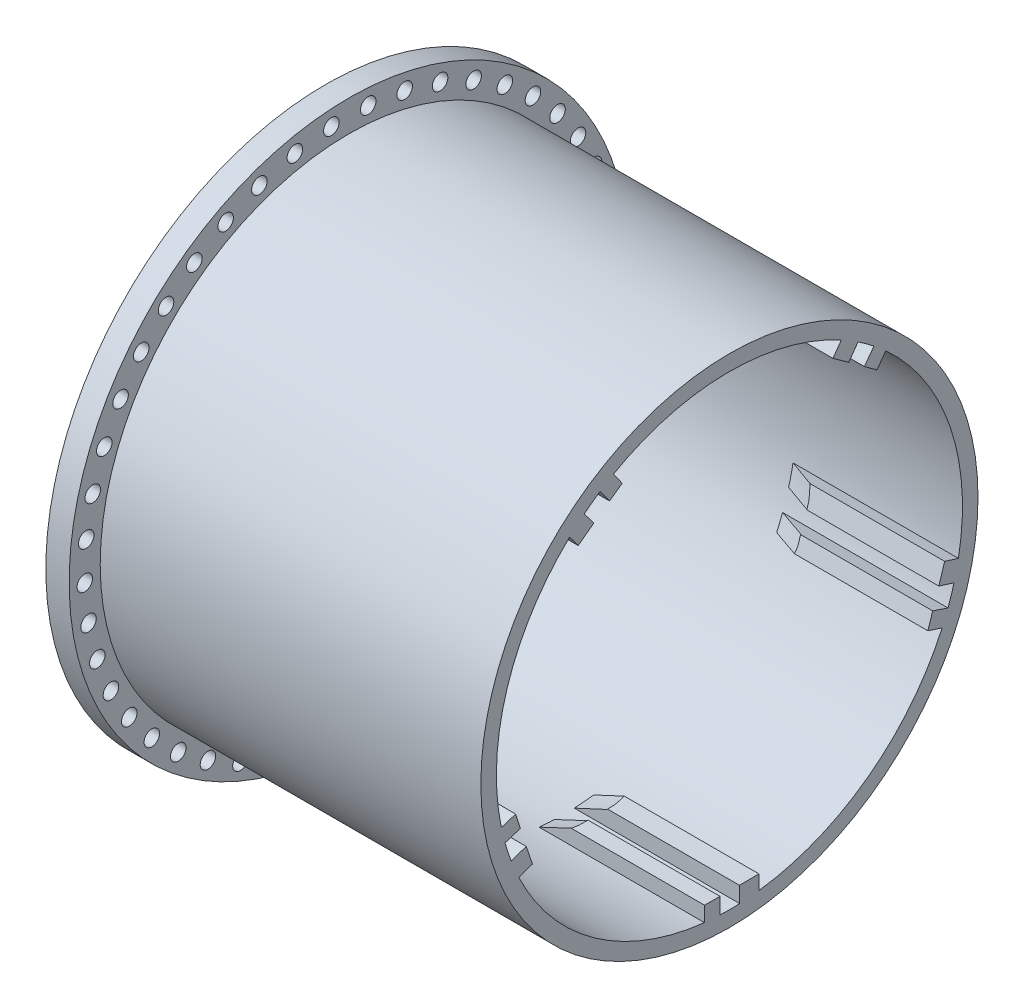
SolidWorks part; units mm, degrees
material "ABS"
ref_plane "Front Plane" through (0, 0, 0) normal (0, 0, 1) x (1, 0, 0)
ref_plane "Top Plane" through (0, 0, 0) normal (0, 1, 0) x (1, 0, 0)
ref_plane "Right Plane" through (0, 0, 0) normal (1, 0, 0) x (0, 0, -1)
sketch "Sketch1" plane through (0, 0, 0) normal (1, 0, 0) x (0, 0, -1)
  line L0 (0, 0) -> (20.089, 27.4305) construction
  line L1 (-2, 1.5) -> (2, 1.5)
  line L3 (-2, -1.5) -> (2, -1.5)
  line L5 (-2, 1.5) -> (2, -1.5) construction
  line L6 (-2, -1.5) -> (2, 1.5) construction
  circle A0 centre (0, 0) radius 30
  arc A1 (-2, 1.5) -> (-2, -1.5) centre (0, 0) ccw
  arc A2 (2, -1.5) -> (2, 1.5) centre (0, 0) ccw
  circle A3 centre (20.089, 27.4305) radius 1
  circle A4 centre (23.7111, 24.3677) radius 1
  circle A5 centre (26.8717, 20.8306) radius 1
  circle A6 centre (29.5092, 16.888) radius 1
  circle A7 centre (31.5724, 12.6168) radius 1
  circle A8 centre (33.0211, 8.1) radius 1
  circle A9 centre (33.827, 3.4255) radius 1
  circle A10 centre (33.9745, -1.3156) radius 1
  circle A11 centre (33.4608, -6.0312) radius 1
  circle A12 centre (32.2958, -10.6293) radius 1
  circle A13 centre (30.5022, -15.0206) radius 1
  circle A14 centre (28.1149, -19.1195) radius 1
  circle A15 centre (25.1803, -22.8463) radius 1
  circle A16 centre (21.7557, -26.1283) radius 1
  circle A17 centre (17.9076, -28.9019) radius 1
  circle A18 centre (13.711, -31.1129) radius 1
  circle A19 centre (9.2475, -32.7183) radius 1
  circle A20 centre (4.604, -33.6868) radius 1
  circle A21 centre (-0.1292, -33.9998) radius 1
  circle A22 centre (-4.8597, -33.6509) radius 1
  circle A23 centre (-9.4957, -32.6471) radius 1
  circle A24 centre (-13.9469, -31.0078) radius 1
  circle A25 centre (-18.1267, -28.765) radius 1
  circle A26 centre (-21.9536, -25.9623) radius 1
  circle A27 centre (-25.3532, -22.6543) radius 1
  circle A28 centre (-28.2593, -18.9054) radius 1
  circle A29 centre (-30.6154, -14.7884) radius 1
  circle A30 centre (-32.3756, -10.3837) radius 1
  circle A31 centre (-33.5056, -5.7768) radius 1
  circle A32 centre (-33.9836, -1.0575) radius 1
  circle A33 centre (-33.8, 3.6824) radius 1
  circle A34 centre (-32.9586, 8.3506) radius 1
  circle A35 centre (-31.4756, 12.8563) radius 1
  circle A36 centre (-29.3801, 17.1117) radius 1
  circle A37 centre (-26.7127, 21.0341) radius 1
  circle A38 centre (-23.5253, 24.5471) radius 1
  circle A39 centre (-19.8801, 27.5823) radius 1
  circle A40 centre (-15.8479, 30.0806) radius 1
  circle A41 centre (-11.5072, 31.9935) radius 1
  circle A42 centre (-6.9426, 33.2836) radius 1
  circle A43 centre (-2.2429, 33.9259) radius 1
  circle A44 centre (2.5005, 33.9079) radius 1
  circle A45 centre (7.1953, 33.2299) radius 1
  circle A46 centre (11.75, 31.9051) radius 1
  circle A47 centre (16.076, 29.9594) radius 1
  circle A48 centre (0, 0) radius 4.25
  circle A49 centre (0, 0) radius 36
  circle A50 centre (0, 0) radius 32
  dimension "D1" = 60
  dimension "D4" = 2
  dimension "D7" = 8.5
  dimension "D8" = 72
  dimension "D2" = 4
  dimension "D3" = 3
  dimension "D5" = 34
  dimension "D9" = 2
  dimension "D6" = 45
extrude "Boss-Extrude1" add sketch "Sketch1" along normal blind 3 contours A0 A48 | A50 A0 | A49 A50 A3 A4 A5 A6 A7 A8 A9 A10 A11 A12 A13 A14 A15 A16 A17 A18 A19 A20 A21 A22 A23 A24 A25 A26 region at (0, 0, 29.1515) region at (0, 0, 34.9818) region at (0, 0, 31.0949)
sketch "Sketch2" plane through (3, 0, 0) normal (1, 0, 0) x (0, 0, -1)
  line L0 (-26.1553, -9.8616) -> (-28.0974, -10.5135)
  line L1 (-1.2034, -27.9057) -> (-1.2173, -29.9753)
  line L2 (1.2965, -27.9225) -> (1.3164, -29.9711)
  line L3 (-26.9118, -7.4788) -> (-28.8844, -8.1051)
  line L4 (-17.4614, 21.8277) -> (-18.6815, 23.4734)
  line L5 (-15.429, 23.2835) -> (-16.6342, 24.9661)
  line L6 (15.3635, 23.3519) -> (16.5516, 25.0209)
  line L7 (17.3761, 21.8688) -> (18.6039, 23.535)
  line L8 (26.9566, -7.3954) -> (28.911, -8.0096)
  line L9 (26.168, -9.7678) -> (28.132, -10.4206)
  line L11 (-27.517, -5.5726) -> (-29.3612, -6.1581)
  line L13 (-26.1553, -9.8616) -> (-28.1279, -10.4879)
  line L14 (-25.3597, -12.2317) -> (-27.1214, -12.823)
  line L15 (-26.9118, -7.4788) -> (-27.517, -5.5726)
  line L16 (-26.1553, -9.8616) -> (-25.3597, -12.2317)
  line L17 (-25.3597, -12.2317) -> (-27.3019, -12.8836) construction
  line L18 (-27.517, -5.5726) -> (-29.4896, -6.1989) construction
  line L19 (-13.8031, 24.4482) -> (-14.9298, 26.0212)
  line L20 (-15.429, 23.2835) -> (-13.8031, 24.4482)
  line L21 (-15.429, 23.2835) -> (-16.6342, 24.9661)
  line L22 (-17.4614, 21.8277) -> (-18.6815, 23.4734)
  line L23 (-17.4614, 21.8277) -> (-19.4696, 20.3387)
  line L24 (-19.4696, 20.3387) -> (-20.5764, 21.8315)
  line L25 (18.9862, 20.6824) -> (20.134, 22.2401)
  line L26 (17.3761, 21.8688) -> (18.9862, 20.6824)
  line L27 (17.3761, 21.8688) -> (18.6039, 23.535)
  line L28 (15.3635, 23.3519) -> (16.5516, 25.0209)
  line L29 (15.3635, 23.3519) -> (13.3269, 24.8017)
  line L30 (13.3269, 24.8017) -> (14.4045, 26.3156)
  line L31 (25.5372, -11.6657) -> (27.3733, -12.276)
  line L32 (26.168, -9.7678) -> (25.5372, -11.6657)
  line L33 (26.168, -9.7678) -> (28.132, -10.4206)
  line L34 (26.9566, -7.3954) -> (28.911, -8.0096)
  line L35 (26.9566, -7.3954) -> (27.7061, -5.0104)
  line L36 (27.7061, -5.0104) -> (29.4788, -5.5676)
  line L37 (-3.2034, -27.8922) -> (-3.2164, -29.8271)
  line L38 (-1.2034, -27.9057) -> (-3.2034, -27.8922)
  line L39 (-1.2034, -27.9057) -> (-1.2173, -29.9753)
  line L40 (1.2965, -27.9225) -> (1.3164, -29.9711)
  line L41 (1.2965, -27.9225) -> (3.7964, -27.8983)
  line L42 (3.7964, -27.8983) -> (3.8144, -29.7565)
  circle A2 centre (0, 0) radius 30 construction
  arc A3 (-1.2173, -29.9753) -> (1.3164, -29.9711) centre (0, 0) ccw
  arc A5 (-28.8844, -8.1051) -> (-28.0974, -10.5135) centre (0, 0) ccw
  arc A7 (-16.6342, 24.9661) -> (-18.6815, 23.4734) centre (0, 0) ccw
  arc A9 (18.6039, 23.535) -> (16.5516, 25.0209) centre (0, 0) ccw
  arc A11 (28.132, -10.4206) -> (28.911, -8.0096) centre (0, 0) ccw
  arc A12 (-28.8844, -8.1051) -> (-28.0974, -10.5135) centre (0, 0) ccw
  circle A13 centre (0, 0) radius 32 construction
  circle A14 centre (0, 0) radius 32
  arc A15 (-27.1214, -12.823) -> (-3.2164, -29.8271) centre (0, 0) ccw
  arc A20 (28.132, -10.4206) -> (28.911, -8.0096) centre (0, 0) ccw
  arc A21 (29.4788, -5.5676) -> (20.134, 22.2401) centre (0, 0) ccw
  arc A22 (14.4045, 26.3156) -> (-14.9298, 26.0212) centre (0, 0) ccw
  arc A23 (18.6039, 23.535) -> (16.5516, 25.0209) centre (0, 0) ccw
  arc A24 (-20.5764, 21.8315) -> (-29.3612, -6.1581) centre (0, 0) ccw
  arc A25 (-16.6342, 24.9661) -> (-18.6815, 23.4734) centre (0, 0) ccw
  arc A26 (-1.2173, -29.9753) -> (1.3164, -29.9711) centre (0, 0) ccw
  arc A27 (3.8144, -29.7565) -> (27.3733, -12.276) centre (0, 0) ccw
  dimension "D2" = 2
  dimension "D1" = 5
  dimension "D3" = 2.5
  dimension "D4" = 5
extrude "Boss-Extrude4" add sketch "Sketch2" along normal blind 49 contours A14 A27 L42 L41 L2 A3 L1 L38 L37 A15 L14 L16 L0 A5 L3 L15 L11 A24 L24 L23 L4 A7 L5 L20 L19 A22 L30 L29 L6 A9 L7 L26 L25 A21 L36 L35 L8 A11 L9 L32 L31 region at (3, 0, 31.0949)
extrude "Cut-Extrude3" cut sketch "Sketch1<7>" along normal blind 3 contours A0
sketch "Sketch1<7>" plane through (0, 0, 0) normal (1, 0, 0) x (0, 0, -1) same geometry as "Sketch1"
sketch "Sketch3" plane through (52, 0, 0) normal (1, 0, 0) x (0, 0, -1)
  circle A2 centre (0, 0) radius 30
  circle A3 centre (0, 0) radius 30
  dimension "D1" = 2
extrude "Cut-Extrude4" cut sketch "Sketch3" against normal through all from offset 17 offset against normal yes
chamfer "Chamfer1" [suppressed] distance 2 angle 60
chamfer "Chamfer2" distance 2 angle 65 10 edges at (35, 25.5078, 15.7908) (35, 22.9003, -19.3798) (35, 25.6907, -15.4916) (35, -6.7945, -29.2204) (35, -11.3547, -27.7682) (35, -29.8899, -2.5676) (35, -29.9179, 2.2181) (35, -7.1356, 29.139) (35, -11.6785, 27.6336) (35, 22.6722, 19.6461) first distance on face at (35, 24.6833, 15.2012) first distance on face at (35, 22.0848, -18.7778) first distance on face at (35, 24.8781, -14.915) first distance on face at (35, -6.4973, -28.2695) first distance on face at (35, -11.0341, -26.8065) first distance on face at (35, -28.8937, -2.5565) first distance on face at (35, -28.9042, 2.2104) first distance on face at (35, -6.8297, 28.1726) first distance on face at (35, -11.36, 26.6895) first distance on face at (35, 21.8728, 19.0515)
